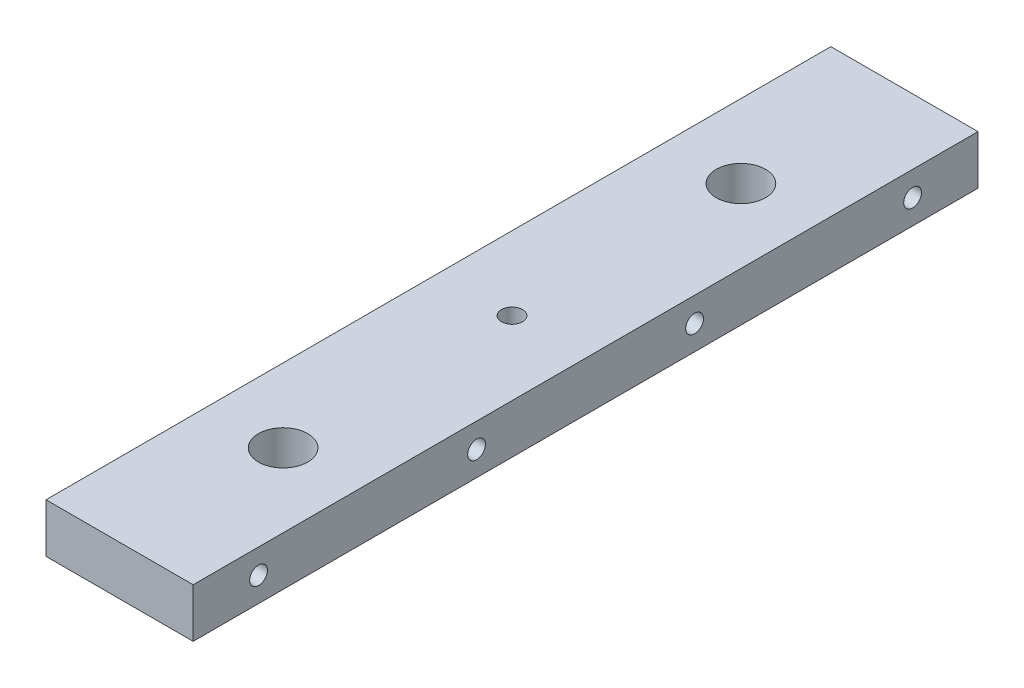
SolidWorks part; units mm, degrees
ref_plane "Front Plane" through (0, 0, 0) normal (0, 0, 1) x (1, 0, 0)
ref_plane "Top Plane" through (0, 0, 0) normal (0, 1, 0) x (1, 0, 0)
ref_plane "Right Plane" through (0, 0, 0) normal (1, 0, 0) x (0, 0, -1)
sketch "Sketch2" plane through (0, 0, 0) normal (0, 1, 0) x (1, 0, 0)
  line L0 (0, 0) -> (0, 152.4)
  line L1 (0, 152.4) -> (28.575, 152.4)
  line L2 (28.575, 152.4) -> (28.575, 0)
  line L3 (28.575, 0) -> (0, 0)
  dimension "D1" = 152.4
  dimension "D2" = 28.575
extrude "Boss-Extrude1" add sketch "Sketch2" along normal blind 9.525
sketch "Sketch3" plane through (0, 0, 0) normal (-1, 0, 0) x (0, 0, 1)
  line L3 (-152.4, 9.525) -> (0, 9.525) construction
  line L4 (-152.4, 9.525) -> (-152.4, 0) construction
  point P6 (-139.7, 4.7625)
  point P14 (-139.7, 4.7625)
  dimension "D1" = 4.7625
  dimension "D2" = 12.7
sketch "Sketch8" plane through (0, 0, 0) normal (-1, 0, 0) x (0, 0, 1)
  point P0 (-139.7, 4.7625)
hole_wizard "#5 Clearance Hole3" positions "Sketch8" profile "Sketch9" hole size "#5" standard "ANSI Inch"
sketch "Sketch9" plane through (0, 4.7625, -139.7) normal (0, 1, 0) x (0, 0, 1)
  line L0 (0, 0) -> (0, 13.7378)
  line L1 (0, 13.7378) -> (1.7272, 12.7)
  line L2 (1.7272, 12.7) -> (1.7272, 0)
  line L5 (1.7272, 0) -> (0, 0)
  line L10 (0, 13.7378) -> (-1.7272, 12.7) construction
  line L11 (0, -6.35) -> (0, 107.95) construction
  dimension "Hole Dia." = 3.4544
  dimension "Hole Depth" = 12.7
  dimension "Drill Angle" = 118
pattern_linear "LPattern1" count 4 spacing 42.3333 along (0, 0, 1) of "#5 Clearance Hole3"
sketch "Sketch10" plane through (28.575, 0, 0) normal (1, 0, 0) x (0, 0, -1)
  line L0 (0, 9.525) -> (0, 0) construction
  line L1 (0, 9.525) -> (152.4, 9.525) construction
  point P0 (12.7, 4.7625)
  point P1 (12.7, 4.7625)
  point P5 (0, 4.7625)
  point P9 (12.7, 4.7625)
  dimension "D1" = 12.7
  dimension "D2" = 4.7625
hole_wizard "#5 Clearance Hole4" positions "Sketch10" profile "Sketch11" hole size "#5" standard "ANSI Inch"
sketch "Sketch11" plane through (28.575, 4.7625, -12.7) normal (0, 1, 0) x (0, 0, -1)
  line L0 (0, 0) -> (0, 13.7378)
  line L1 (0, 13.7378) -> (1.7272, 12.7)
  line L2 (1.7272, 12.7) -> (1.7272, 0)
  line L5 (1.7272, 0) -> (0, 0)
  line L10 (0, 13.7378) -> (-1.7272, 12.7) construction
  line L11 (0, -6.35) -> (0, 107.95) construction
  dimension "Hole Dia." = 3.4544
  dimension "Hole Depth" = 12.7
  dimension "Drill Angle" = 118
pattern_linear "LPattern2" count 4 spacing 42.3333 along (0, 0, -1) of "#5 Clearance Hole4"
sketch "Sketch12" plane through (0, 9.525, 0) normal (0, 1, 0) x (1, 0, 0)
  line L0 (28.575, 0) -> (28.575, 152.4) construction
  line L2 (0, 0) -> (28.575, 0) construction
  circle A0 centre (14.2875, 76.2) radius 2.05
  circle A1 centre (14.2875, 31.75) radius 4.7879
  circle A2 centre (14.2875, 120.65) radius 4.7879
  point P0 (14.2875, 120.65)
  point P1 (14.2875, 76.2)
  point P2 (14.2875, 31.75)
  dimension "D7" = 4.1
  dimension "D8" = 9.5758
  dimension "D9" = 9.5758
  dimension "D1" = 14.2875
  dimension "D2" = 14.2875
  dimension "D3" = 14.2875
  dimension "D4" = 76.2
  dimension "D5" = 44.45
  dimension "D6" = 44.45
extrude "Cut-Extrude1" cut sketch "Sketch12" against normal through all
